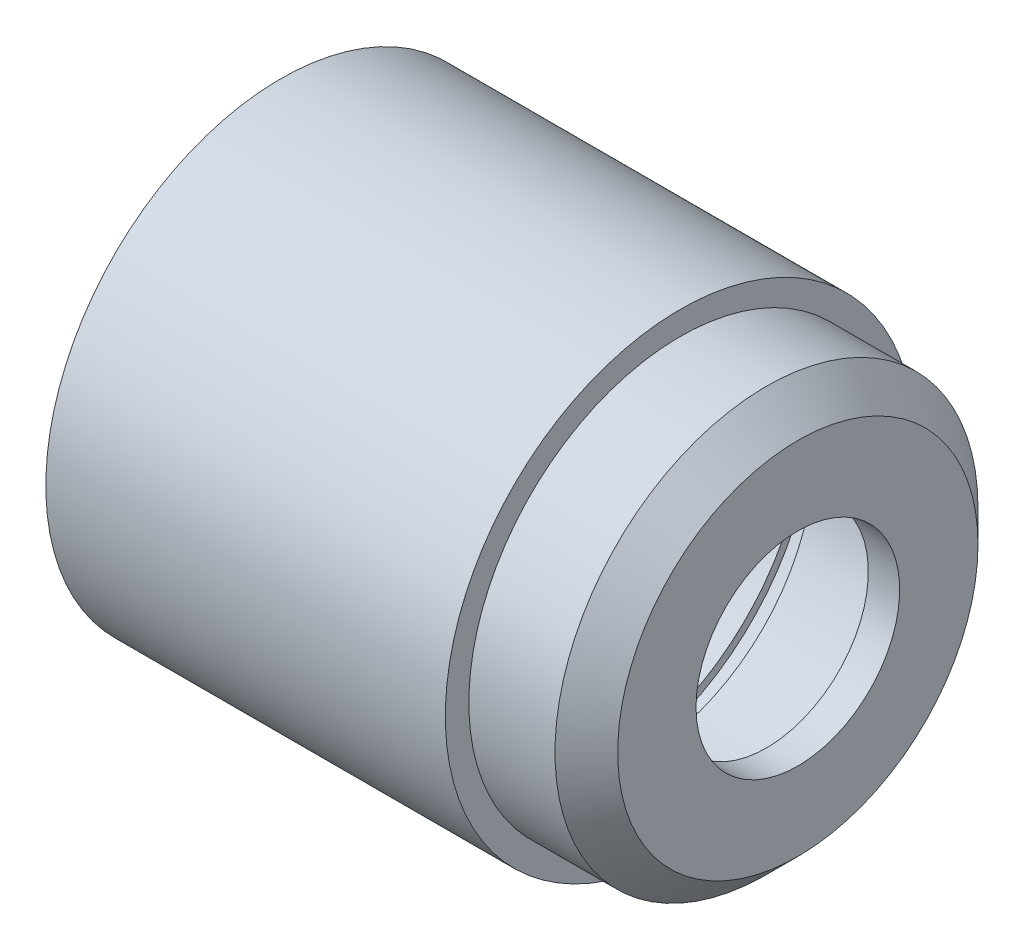
SolidWorks part; units mm, degrees
material "Alliage de zinc AC41A, brut"
ref_plane "Plan de face" through (0, 0, 0) normal (0, 0, 1) x (1, 0, 0)
ref_plane "Plan de dessus" through (0, 0, 0) normal (0, 1, 0) x (1, 0, 0)
ref_plane "Plan de droite" through (0, 0, 0) normal (1, 0, 0) x (0, 0, -1)
sketch "Sketch1" plane through (0, 0, 0) normal (1, 0, 0) x (0, 0, -1)
  circle A0 centre (0, 0) radius 15
  dimension "D1" = 30
extrude "Boss-Extrude1" add sketch "Sketch1" along normal blind 25.5
sketch "Sketch2" plane through (25.5, 0, 0) normal (1, 0, 0) x (0, 0, -1)
  circle A0 centre (0, 0) radius 13.5
  dimension "D1" = 27
extrude "Boss-Extrude2" add sketch "Sketch2" along normal blind 7.5
sketch "Sketch3" plane through (0, 0, 0) normal (-1, 0, 0) x (0, 0, 1)
  circle A0 centre (0, 0) radius 14
  dimension "D1" = 28
extrude "Cut-Extrude1" cut sketch "Sketch3" against normal blind 6.5
sketch "Sketch4" plane through (6.5, 0, 0) normal (-1, 0, 0) x (0, 0, 1)
  circle A0 centre (0, 0) radius 13
  dimension "D1" = 26
extrude "Cut-Extrude2" cut sketch "Sketch4" against normal blind 14
sketch "Sketch5" plane through (20.5, 0, 0) normal (-1, 0, 0) x (0, 0, 1)
  circle A0 centre (0, 0) radius 13.5
  dimension "D1" = 27
extrude "Cut-Extrude3" cut sketch "Sketch5" against normal blind 2.5
sketch "Sketch6" plane through (23, 0, 0) normal (-1, 0, 0) x (0, 0, 1)
  circle A0 centre (0, 0) radius 11
  dimension "D1" = 22
extrude "Cut-Extrude4" cut sketch "Sketch6" against normal blind 6
sketch "Sketch7" plane through (29, 0, 0) normal (-1, 0, 0) x (0, 0, 1)
  circle A0 centre (0, 0) radius 11.5
  dimension "D1" = 23
extrude "Cut-Extrude5" cut sketch "Sketch7" against normal blind 1
sketch "Sketch9" plane through (30, 0, 0) normal (-1, 0, 0) x (0, 0, 1)
  circle A0 centre (0, 0) radius 10
  dimension "D1" = 20
extrude "Cut-Extrude6" cut sketch "Sketch9" against normal blind 1
sketch "Sketch10" plane through (31, 0, 0) normal (-1, 0, 0) x (0, 0, 1)
  circle A0 centre (0, 0) radius 6.5
  dimension "D1" = 13
extrude "Cut-Extrude7" cut sketch "Sketch10" against normal blind 2
chamfer "Chamfer1" distance 2 angle 45 1 edges at (33, 0, -13.5)
